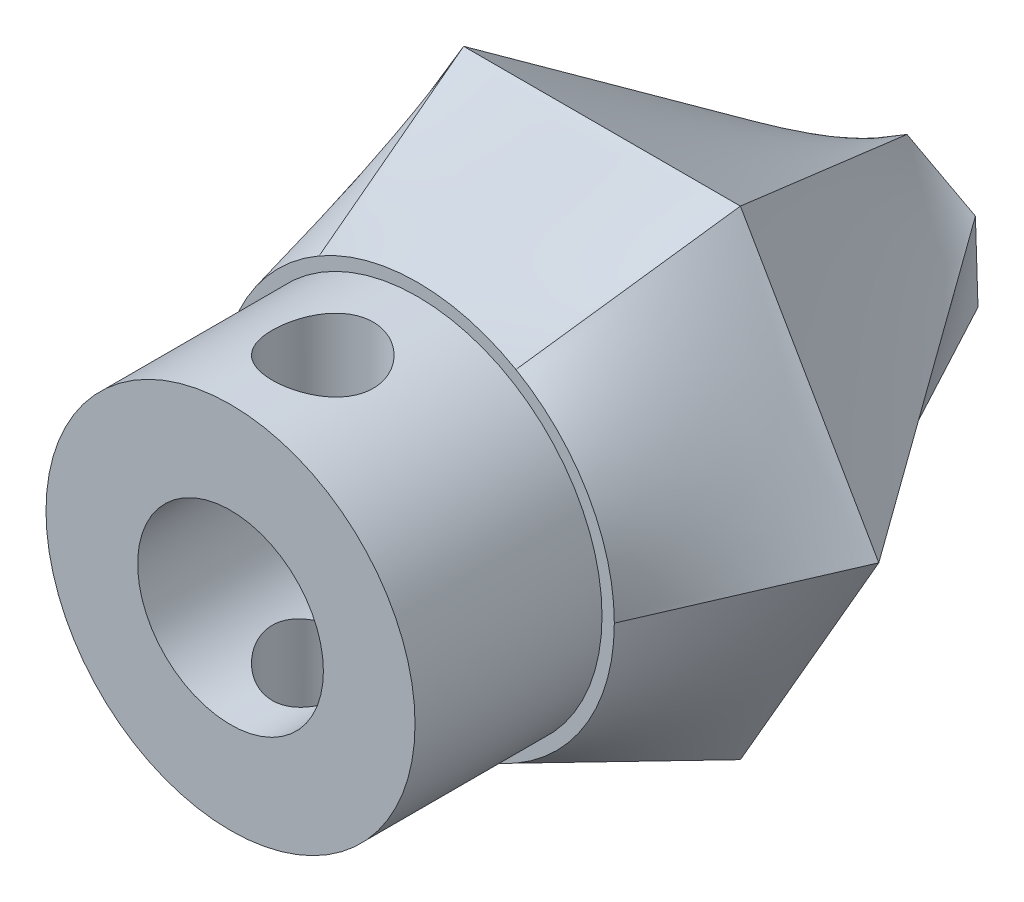
SolidWorks part; units mm, degrees
ref_plane "정면" through (0, 0, 0) normal (0, 0, 1) x (1, 0, 0)
ref_plane "윗면" through (0, 0, 0) normal (0, 1, 0) x (1, 0, 0)
ref_plane "우측면" through (0, 0, 0) normal (1, 0, 0) x (0, 0, -1)
sketch "스케치1" plane through (0, 0, 0) normal (0, 0, 1) x (1, 0, 0)
  circle A0 centre (0, 0) radius 7.55
  circle A1 centre (0, 0) radius 15
  dimension "D1" = 15.1
  dimension "D2" = 30
extrude "보스-돌출1" add sketch "스케치1" along normal blind 15.2
sketch "스케치2" plane through (0, 0, 0) normal (0, 1, 0) x (1, 0, 0)
  line L0 (7.55, 0) -> (-7.55, 0) construction
  circle A0 centre (0, -7.7) radius 4.1
  dimension "D2" = 8.2
  dimension "D1" = 7.7
extrude "컷-돌출1" cut sketch "스케치2" against normal through all both and the other way through all
sketch "스케치3" plane through (0, 0, 0) normal (0, 0, 1) x (1, 0, 0)
  circle A0 centre (0, 0) radius 16
  dimension "D1" = 32
ref_plane "평면1" through (0, 0, -15) normal (0, 0, 1) x (1, 0, 0)
sketch "스케치4" plane through (0, 0, -15) normal (0, 0, 1) x (1, 0, 0)
  line L4 (-18.8237, 0) -> (18.8237, 0) construction
  line L5 (0, -18.8237) -> (0, 18.8237) construction
  line L7 (11.25, -19.4856) -> (22.5, 0)
  line L8 (22.5, 0) -> (11.25, 19.4856)
  line L9 (11.25, 19.4856) -> (-11.25, 19.4856)
  line L10 (-11.25, 19.4856) -> (-22.5, 0)
  line L11 (-22.5, 0) -> (-11.25, -19.4856)
  line L12 (-11.25, -19.4856) -> (11.25, -19.4856)
  circle A0 centre (0, 0) radius 19.4856 construction
  point P1 (0, 0)
  dimension "D1" = 45
ref_plane "평면2" through (0, 0, -40) normal (0, 0, 1) x (1, 0, 0)
sketch "스케치6" plane through (0, 0, -40) normal (0, 0, 1) x (1, 0, 0)
  line L1 (0.2105, -6.3026) -> (5.5635, -2.969)
  line L2 (5.5635, -2.969) -> (5.353, 3.3336)
  line L3 (5.353, 3.3336) -> (-0.2105, 6.3026)
  line L4 (-0.2105, 6.3026) -> (-5.5635, 2.969)
  line L5 (-5.5635, 2.969) -> (-5.353, -3.3336)
  line L6 (-5.353, -3.3336) -> (0.2105, -6.3026)
  circle A0 centre (0, 0) radius 5.4613 construction
loft "로프트4" add profiles "스케치3", "스케치4" connector at (15.9782, 0.834, 0) connector at (22.5, 0, -15)
sketch "스케치7" plane through (0, 0, -15) normal (0, 0, -1) x (-1, 0, 0)
  line L12 (-11.25, -19.4856) -> (11.25, -19.4856)
  line L13 (11.25, -19.4856) -> (22.5, 0)
  line L14 (22.5, 0) -> (11.25, 19.4856)
  line L15 (11.25, 19.4856) -> (-11.25, 19.4856)
  line L16 (-11.25, 19.4856) -> (-22.5, 0)
  line L17 (-22.5, 0) -> (-11.25, -19.4856)
loft "로프트5" add profiles "스케치7", "스케치6" connector at (22.5, 0, -15) connector at (5.353, 3.3336, -40)
sketch "스케치8" plane through (0, 0, -40) normal (0, 0, -1) x (-1, 0, 0)
  circle A0 centre (0, 0) radius 4
  dimension "D1" = 8
extrude "컷-돌출2" cut sketch "스케치8" against normal blind 6
